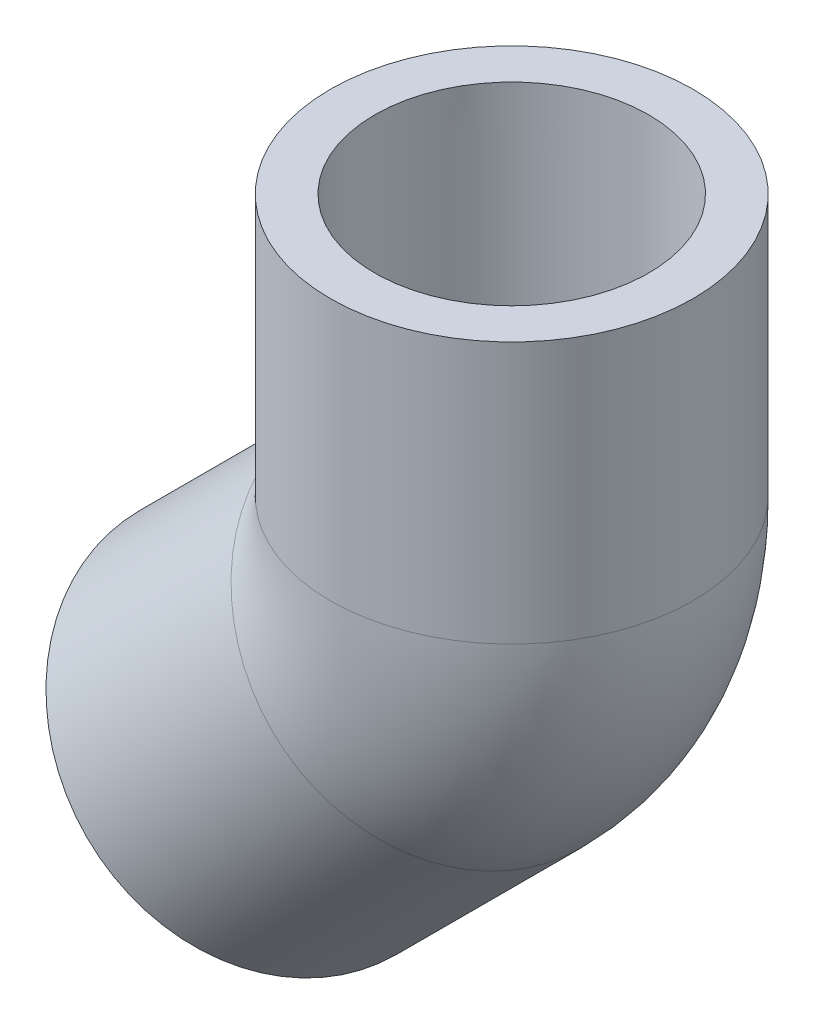
SolidWorks part; units mm, degrees
ref_plane "Front Plane" through (0, 0, 0) normal (0, 0, 1) x (1, 0, 0)
ref_plane "Top Plane" through (0, 0, 0) normal (0, 1, 0) x (1, 0, 0)
ref_plane "Right Plane" through (0, 0, 0) normal (1, 0, 0) x (0, 0, -1)
sketch "Sketch0" plane through (0, 0, 0) normal (0, 0, 1) x (1, 0, 0)
  line L0 (-23.8875, -23.8875) -> (0, 0) construction
  line L1 (0, 0) -> (0, 33.782) construction
  line L2 (-5.7474, -5.7474) -> (0, 0) construction
  line L3 (0, 0) -> (0, 8.128) construction
  line L4 (-36.4598, -11.3151) -> (-11.3151, -36.4598) construction
  line L5 (-15.1407, 3.646) -> (-33.3886, -14.3864) construction
  line L6 (-15.1407, 3.646) -> (3.646, -15.1407) construction
  line L7 (3.646, -15.1407) -> (-14.3864, -33.3886) construction
  line L8 (-33.3886, -14.3864) -> (-14.3864, -33.3886) construction
  line L9 (-17.78, 33.782) -> (17.78, 33.782) construction
  line L10 (-13.4366, 33.782) -> (13.4366, 33.782) construction
  line L11 (13.4366, 33.782) -> (13.2842, 8.128) construction
  line L12 (13.2842, 8.128) -> (-13.2842, 8.128) construction
  line L13 (-13.2842, 8.128) -> (-13.4366, 33.782) construction
  line L14 (-12.4107, 0.916) -> (0.916, -12.4107) construction
  line L18 (-9.4234, 8.128) -> (9.4234, 8.128) construction
  dimension "D1" = 45
  dimension "H" = 33.782
  dimension "J" = 8.128
  dimension "M" = 35.56
  dimension "OD A" = 26.8732
  dimension "OD B" = 26.5684
  dimension "ID" = 18.8468
sketch "Sketch1" plane through (0, 0, 0) normal (0, 0, 1) x (1, 0, 0)
  line L0 (-23.8875, -23.8875) -> (0, 0) construction
  line L1 (-23.8875, -23.8875) -> (0, 0) construction
  line L3 (-11.3151, -36.4598) -> (6.825, -18.3197)
  line L4 (-11.3151, -36.4598) -> (-14.3864, -33.3886)
  line L5 (-14.3864, -33.3886) -> (3.646, -15.1407)
  line L6 (6.825, -18.3197) -> (3.646, -15.1407)
revolve "Revolve1" add sketch "Sketch1" angle 360 about L1
sketch "Sketch2" plane through (0, 0, 0) normal (0, 0, 1) x (1, 0, 0)
  line L0 (13.4366, 33.782) -> (13.2842, 8.128)
  line L1 (13.2842, 8.128) -> (17.78, 8.128)
  line L2 (17.78, 8.128) -> (17.78, 33.782)
  line L3 (17.78, 33.782) -> (13.4366, 33.782)
  line L4 (0, 0) -> (0, 33.782) construction
  line L5 (0, 0) -> (0, 33.782) construction
revolve "Revolve2" add sketch "Sketch2" angle 360 about L5
sketch "Sketch3" plane through (-5.7474, -5.7474, 0) normal (0.7071, 0.7071, 0) x (0, 0, -1)
  circle A0 centre (0, 0) radius 9.4234
  circle A1 centre (0, 0) radius 17.78
sketch "Sketch4" plane through (0, 0, 0) normal (0, 0, 1) x (1, 0, 0)
  line L0 (-23.8875, -23.8875) -> (0, 0) construction
  line L1 (0, 0) -> (0, 33.782) construction
  line L2 (-23.8875, -23.8875) -> (-5.7474, -5.7474) construction
  line L3 (0, 8.128) -> (0, 33.782) construction
  arc A0 (-5.7474, -5.7474) -> (0, 8.128) centre (-19.6227, 8.128) ccw
sweep "Sweep1" add profiles "Sketch3" path "Sketch4"
